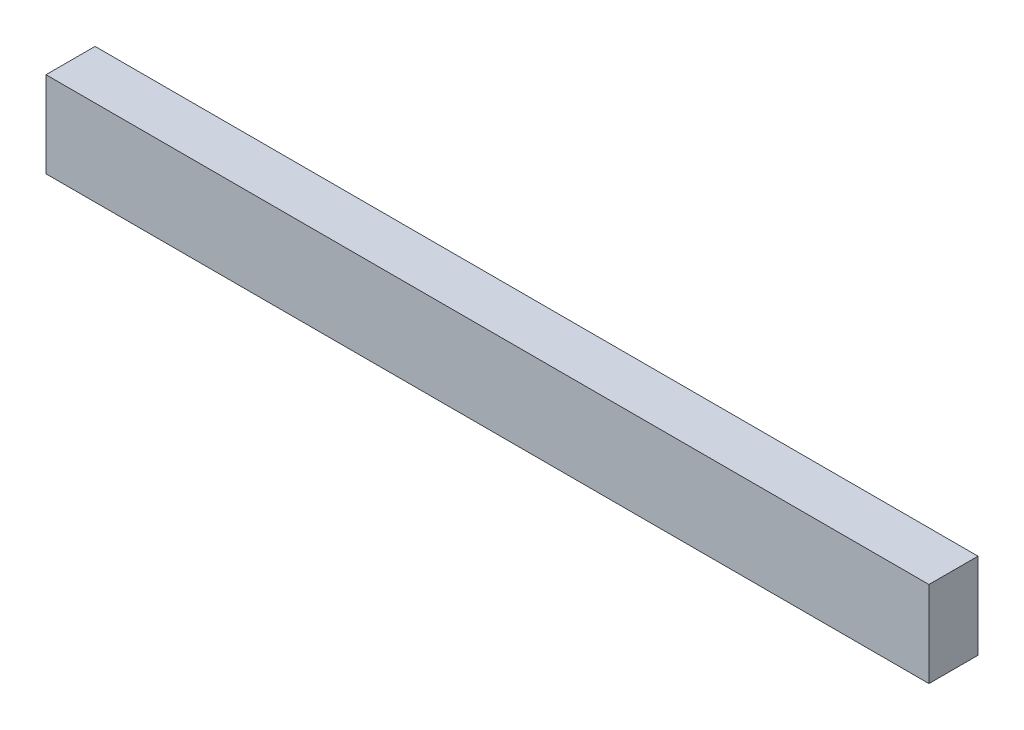
SolidWorks part; units mm, degrees
ref_plane "Front Plane" through (0, 0, 0) normal (0, 0, 1) x (1, 0, 0)
ref_plane "Top Plane" through (0, 0, 0) normal (0, 1, 0) x (1, 0, 0)
ref_plane "Right Plane" through (0, 0, 0) normal (1, 0, 0) x (0, 0, -1)
sketch "Sketch1" plane through (0, 0, 0) normal (0, 0, 1) x (1, 0, 0)
  line L1 (0, 0) -> (228.6, 0)
  line L2 (0, 0) -> (0, 22.225)
  line L3 (0, 22.225) -> (228.6, 22.225)
  line L4 (228.6, 0) -> (228.6, 22.225)
  dimension "D1" = 228.6
  dimension "D2" = 22.225
extrude "Boss-Extrude1" add sketch "Sketch1" along normal blind 12.7
sketch "Sketch5" plane through (0, 0, 0) normal (0, 0, -1) x (-1, 0, 0)
  line L0 (-25.0197, 0) -> (-38.1, 12.7)
  line L1 (0, 0) -> (-228.6, 0) construction
  line L2 (-38.1, 12.7) -> (-203.2, 12.7)
  line L3 (-203.2, 12.7) -> (-215.9, 0)
  line L4 (-215.9, 0) -> (-25.0197, 0)
  line L5 (-228.6, 19.05) -> (-203.2, 22.225)
  line L6 (-228.6, 0) -> (-228.6, 22.225) construction
  line L7 (-234.3089, 18.3364) -> (-228.6, 19.05) construction
  line L8 (-228.6, 22.225) -> (0, 22.225) construction
  line L9 (-277.8821, 12.8897) -> (-235.5911, 18.1761) construction
  line L10 (-228.6, 19.05) -> (-228.6, 22.225)
  line L11 (-228.6, 22.225) -> (-203.2, 22.225)
  line L12 (0, 22.225) -> (0, 0) construction
  line L15 (0, 12.7) -> (0, 0)
  line L16 (0, 0) -> (-25.0197, 0)
  point P22 (-25.4275, 0)
  point P26 (-25.6314, 0)
  point P27 (0, 0)
  point P28 (-25.0197, 0)
  dimension "D1" = 9.525
  dimension "D2" = 38.1
  dimension "D3" = 25.4
  dimension "D4" = 12.7
extrude "Cut-Extrude1" cut sketch "Sketch5" against normal through all rebuild error yes
